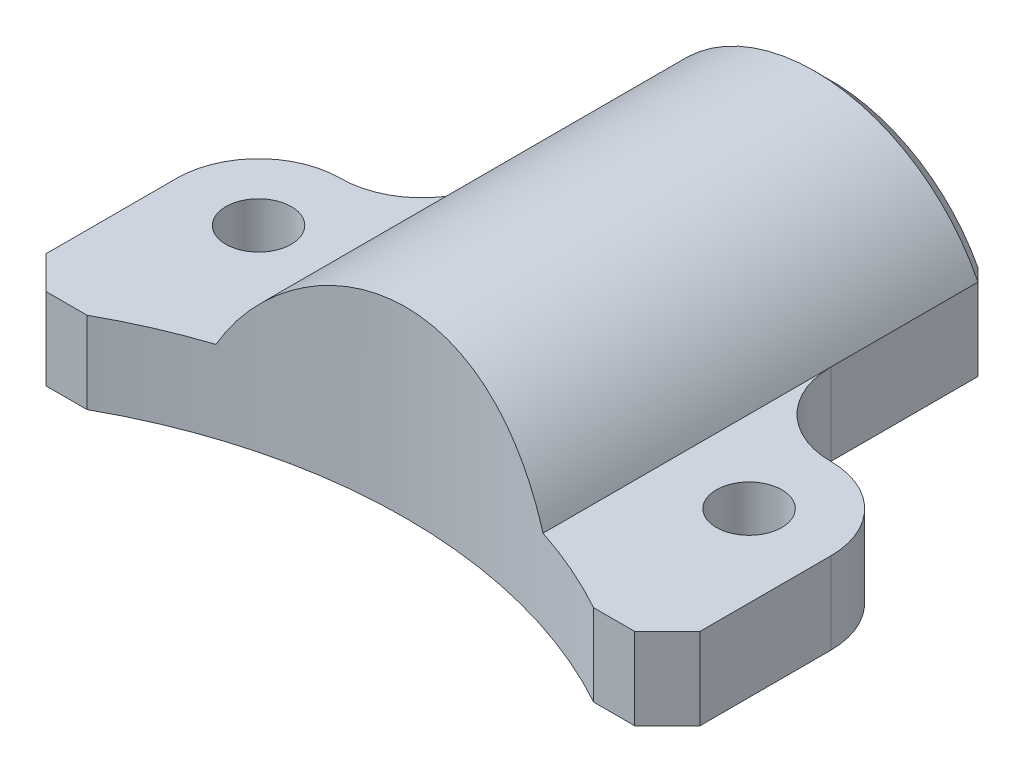
SolidWorks part; units mm, degrees
ref_plane "Front" through (0, 0, 0) normal (0, 0, 1) x (1, 0, 0)
ref_plane "Top" through (0, 0, 0) normal (0, 1, 0) x (1, 0, 0)
ref_plane "Right" through (0, 0, 0) normal (1, 0, 0) x (0, 0, -1)
sketch "Sketch1" plane through (0, 0, 0) normal (0, 1, 0) x (1, 0, 0)
  line L1 (-20, -15) -> (20, -15)
  line L2 (-20, -15) -> (-20, 15)
  line L3 (-20, 15) -> (20, 15)
  line L4 (20, -15) -> (20, 15)
  line L5 (-20, -15) -> (20, 15) construction
  line L6 (-20, 15) -> (20, -15) construction
  point P0 (0, 0)
  dimension "D1" = 30
  dimension "D2" = 40
extrude "Boss-Extrude1" add sketch "Sketch1" along normal blind 5
sketch "Sketch3" plane through (0, 5, 0) normal (0, 1, 0) x (1, 0, 0)
  line L0 (20, 15) -> (-20, 15) construction
  line L1 (-10, 15) -> (10, 15)
  line L2 (-10, 15) -> (-10, -15)
  line L3 (-10, -15) -> (10, -15)
  line L4 (10, 15) -> (10, -15)
  line L5 (-20, -15) -> (20, -15) construction
  line L6 (0, 0) -> (0, 29.2702) construction
  dimension "D1" = 20
extrude "Boss-Extrude2" add sketch "Sketch3" along normal blind 7.5
sketch "Sketch4" plane through (0, 0, -15) normal (0, 0, -1) x (-1, 0, 0)
  line L1 (-10, 12.5) -> (-10, 5) construction
  line L3 (-10, 5) -> (-10, 21.1803)
  line L4 (-10, 21.1803) -> (10, 21.1803)
  line L5 (10, 21.1803) -> (10, 5)
  line L7 (10, 12.5) -> (10, 5) construction
  circle A0 centre (0, 0) radius 11.1803 construction
  arc A1 (-10, 5) -> (10, 5) centre (0, 0) cw
extrude "Cut-Extrude1" cut sketch "Sketch4" against normal through all
sketch "Sketch5" plane through (0, 5, 0) normal (0, 1, 0) x (1, 0, 0)
  line L1 (-20, 15) -> (-10, 15)
  line L2 (-20, 15) -> (-20, 0)
  line L3 (-20, 0) -> (-10, 0)
  line L4 (-10, 15) -> (-10, 0)
  line L6 (20, 15) -> (10, 15)
  line L7 (20, 15) -> (20, 0)
  line L8 (20, 0) -> (10, 0)
  line L9 (10, 15) -> (10, 0)
  line L10 (10, -15) -> (10, 15) construction
  line L11 (-10, 15) -> (-10, -15) construction
extrude "Cut-Extrude2" cut sketch "Sketch5" against normal through all
sketch "Sketch6" plane through (0, 0, -15) normal (0, 0, -1) x (-1, 0, 0)
  circle A0 centre (0, 0) radius 4
  dimension "D1" = 8
extrude "Cut-Extrude3" cut sketch "Sketch6" against normal blind 20
chamfer "Chamfer1" distance 1 angle 45 4 edges at (0, 11.1803, -15) (0, 4, -15) (10, 2.5, -15) (-10, 2.5, -15)
fillet "Fillet1" radius 5 4 edges at (20, 2.5, 0) (10, 2.5, 0) (-20, 2.5, 0) (-10, 2.5, 0)
sketch "Sketch7" plane through (0, 0, 0) normal (0, -1, 0) x (1, 0, 0)
  circle A0 centre (-15, 5) radius 2
  circle A1 centre (15, 5) radius 2
  arc A2 (15, 0) -> (20, 5) centre (15, 5) ccw construction
  arc A3 (-20, 5) -> (-15, 0) centre (-15, 5) ccw construction
  dimension "D1" = 4
extrude "Cut-Extrude4" cut sketch "Sketch7" against normal through all
chamfer "Chamfer2" distance 2 angle 45 2 edges at (-20, 2.5, 15) (20, 2.5, 15)
sketch "Sketch8" plane through (0, 0, 0) normal (0, -1, 0) x (1, 0, 0)
  line L0 (-4, 5) -> (4, 5) construction
  circle A0 centre (0, 43) radius 32
  point P2 (0, 0)
  dimension "D1" = 64
  dimension "D2" = 38
extrude "Cut-Extrude5" cut sketch "Sketch8" against normal through all
